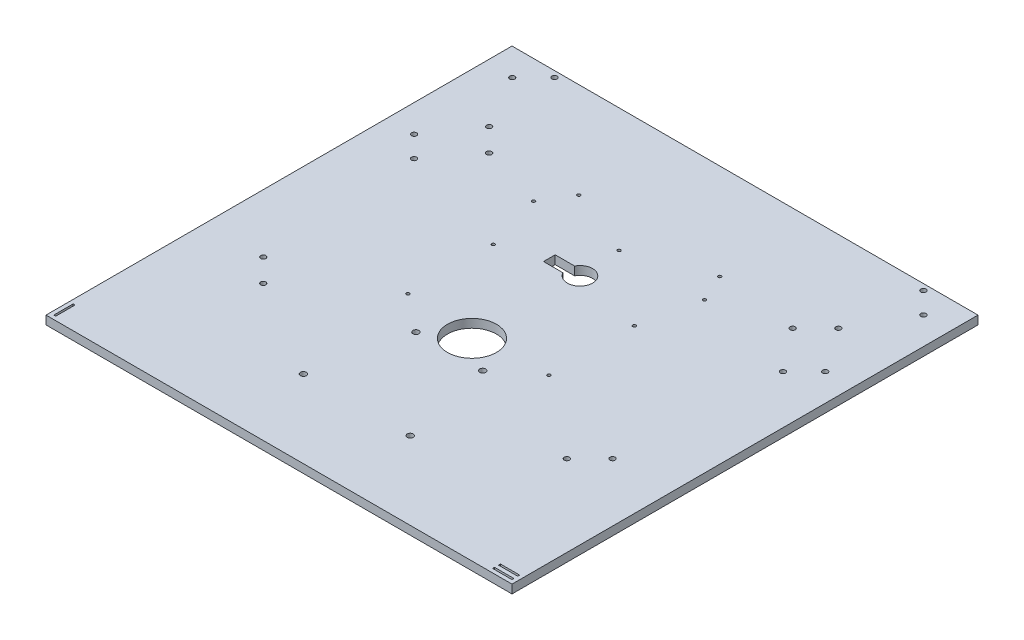
SolidWorks part; units mm, degrees
material "Acrylic (Medium-high impact)"
ref_plane "Front Plane" through (0, 0, 0) normal (0, 0, 1) x (1, 0, 0)
ref_plane "Top Plane" through (0, 0, 0) normal (0, 1, 0) x (1, 0, 0)
ref_plane "Right Plane" through (0, 0, 0) normal (1, 0, 0) x (0, 0, -1)
sketch "Sketch2" plane through (0, 0, 0) normal (0, 1, 0) x (1, 0, 0)
  line L1 (0, 0) -> (304.8, 0)
  line L2 (0, 0) -> (0, 304.8)
  line L3 (0, 304.8) -> (304.8, 304.8)
  line L4 (304.8, 0) -> (304.8, 304.8)
  dimension "D1" = 304.8
  dimension "D2" = 304.8
extrude "Boss-Extrude1" add sketch "Sketch2" along normal blind 5.588
sketch "Sketch4" plane through (0, 5.588, 0) normal (0, 1, 0) x (1, 0, 0)
  line L0 (0, 304.8) -> (0, 0) construction
  line L1 (2.54, 2.54) -> (3.81, 2.54)
  line L2 (2.54, 2.54) -> (2.54, 15.24)
  line L3 (2.54, 15.24) -> (3.81, 15.24)
  line L4 (3.81, 2.54) -> (3.81, 15.24)
  line L5 (2.54, 302.26) -> (3.81, 302.26) construction
  line L6 (2.54, 302.26) -> (2.54, 289.56) construction
  line L7 (2.54, 289.56) -> (3.81, 289.56) construction
  line L8 (3.81, 302.26) -> (3.81, 289.56) construction
  line L9 (6.35, 302.26) -> (7.62, 302.26) construction
  line L10 (6.35, 302.26) -> (6.35, 289.56) construction
  line L11 (6.35, 289.56) -> (7.62, 289.56) construction
  line L12 (7.62, 302.26) -> (7.62, 289.56) construction
  line L13 (304.8, 304.8) -> (0, 304.8) construction
  line L14 (0, 0) -> (304.8, 0) construction
  line L15 (304.8, 0) -> (304.8, 304.8) construction
  line L16 (302.26, 2.54) -> (289.56, 2.54)
  line L17 (302.26, 2.54) -> (302.26, 3.81)
  line L18 (302.26, 3.81) -> (289.56, 3.81)
  line L19 (289.56, 2.54) -> (289.56, 3.81)
  line L20 (302.26, 6.35) -> (289.56, 6.35)
  line L21 (302.26, 6.35) -> (302.26, 7.62)
  line L22 (302.26, 7.62) -> (289.56, 7.62)
  line L23 (289.56, 6.35) -> (289.56, 7.62)
  dimension "D1" = 12.7
  dimension "D2" = 1.27
  dimension "D3" = 2.54
  dimension "D4" = 2.54
  dimension "D5" = 2.54
  dimension "D6" = 2.54
  dimension "D7" = 2.54
  dimension "D8" = 2.54
  dimension "D9" = 2.54
  dimension "D10" = 2.54
extrude "Cut-Extrude1" cut sketch "Sketch4" against normal through all
sketch "Sketch5" plane through (0, 5.588, 0) normal (0, 1, 0) x (1, 0, 0)
  line L0 (0, 304.8) -> (0, 0) construction
  line L1 (34.5465, 268.1122) -> (263.4005, 268.1122)
  line L2 (34.5465, 268.1122) -> (34.5465, 281.0662)
  line L3 (34.5465, 281.0662) -> (263.4005, 281.0662)
  line L4 (263.4005, 268.1122) -> (263.4005, 281.0662)
  line L5 (304.8, 0) -> (304.8, 304.8) construction
  line L6 (304.8, 304.8) -> (0, 304.8) construction
  dimension "D1" = 34.5465
  dimension "D2" = 41.3995
  dimension "D3" = 23.7338
  dimension "D4" = 12.954
extrude "Cut-Extrude2" cut sketch "Sketch5" against normal blind 0.254
sketch "Sketch6" plane through (0, 5.588, 0) normal (0, 1, 0) x (1, 0, 0)
  circle A0 centre (152.48, 126.1263) radius 15.748 construction
  circle A1 centre (152.48, 126.1263) radius 15.748 construction
  circle A2 centre (152.48, 126.1263) radius 16.002
  circle A3 centre (31.75, 300.8321) radius 1.7 construction
  circle A4 centre (17.9387, 287.0209) radius 1.7 construction
  circle A5 centre (273.05, 300.8321) radius 1.7 construction
  circle A6 centre (286.8612, 287.0209) radius 1.7 construction
  circle A7 centre (286.8612, 222.7817) radius 1.7 construction
  circle A8 centre (273.05, 208.9705) radius 1.7 construction
  circle A9 centre (31.75, 208.9705) radius 1.7 construction
  circle A10 centre (17.9388, 222.7817) radius 1.7 construction
  circle A11 centre (31.75, 300.8321) radius 1.7
  circle A12 centre (17.9387, 287.0209) radius 1.7
  circle A13 centre (273.05, 300.8321) radius 1.7
  circle A14 centre (286.8612, 287.0209) radius 1.7
  circle A15 centre (286.8612, 222.7817) radius 1.7
  circle A16 centre (273.05, 208.9705) radius 1.7
  circle A17 centre (31.75, 208.9705) radius 1.7
  circle A18 centre (17.9388, 222.7817) radius 1.7
  circle A19 centre (38.1788, 103.933) radius 1.7 construction
  circle A20 centre (53.133, 88.9788) radius 1.7 construction
  circle A21 centre (251.667, 88.9788) radius 1.7 construction
  circle A22 centre (266.6212, 103.933) radius 1.7 construction
  circle A23 centre (266.6212, 251.667) radius 1.7 construction
  circle A24 centre (251.667, 236.7127) radius 1.7 construction
  circle A25 centre (53.133, 236.7127) radius 1.7 construction
  circle A26 centre (38.1788, 251.667) radius 1.7 construction
  circle A27 centre (38.1788, 103.933) radius 1.7
  circle A28 centre (53.133, 88.9788) radius 1.7
  circle A29 centre (251.667, 88.9788) radius 1.7
  circle A30 centre (266.6212, 103.933) radius 1.7
  circle A31 centre (266.6212, 251.667) radius 1.7
  circle A32 centre (251.667, 236.7127) radius 1.7
  circle A33 centre (53.133, 236.7127) radius 1.7
  circle A34 centre (38.1788, 251.667) radius 1.7
  circle A35 centre (117.555, 50.8216) radius 4.5 construction
  circle A36 centre (187.405, 50.8216) radius 4.5 construction
  circle A37 centre (174.3081, 111.328) radius 4.5 construction
  circle A38 centre (130.6519, 111.328) radius 4.5 construction
  circle A39 centre (117.555, 50.8216) radius 4.5 construction
  circle A40 centre (187.405, 50.8216) radius 4.5 construction
  circle A41 centre (174.3081, 111.328) radius 4.5 construction
  circle A42 centre (130.6519, 111.328) radius 4.5 construction
  circle A43 centre (130.6519, 111.328) radius 1.96
  circle A44 centre (174.3081, 111.328) radius 1.96
  circle A45 centre (187.405, 50.8216) radius 1.96
  circle A46 centre (117.555, 50.8216) radius 1.96
  dimension "D1" = 0.254
  dimension "D2" = 2.54
extrude "Cut-Extrude3" cut sketch "Sketch6" against normal through all
sketch "Sketch7" plane through (0, 5.588, 0) normal (0, 1, 0) x (1, 0, 0)
  line L0 (152.4, 304.8) -> (152.4, 0) construction
  line L1 (304.8, 304.8) -> (0, 304.8) construction
  line L2 (0, 0) -> (304.8, 0) construction
  line L4 (145.0768, 200.66) -> (132.3768, 200.66)
  line L5 (145.0768, 200.66) -> (145.0768, 193.04) construction
  line L6 (145.0768, 193.04) -> (132.3768, 193.04)
  line L7 (132.3768, 200.66) -> (132.3768, 193.04)
  circle A0 centre (152.4, 196.85) radius 8.255 construction
  arc A1 (145.0768, 200.66) -> (145.0768, 193.04) centre (152.4, 196.85) cw
  dimension "D2" = 16.51
  dimension "D1" = 107.95
  dimension "D3" = 7.62
  dimension "D4" = 12.7
extrude "Cut-Extrude4" cut sketch "Sketch7" against normal through all
sketch "Sketch8" plane through (0, 5.588, 0) normal (0, 1, 0) x (1, 0, 0)
  circle A0 centre (94.94, 223.995) radius 0.762 construction
  circle A1 centre (150.82, 223.995) radius 0.762 construction
  circle A2 centre (206.7, 223.995) radius 0.762 construction
  circle A3 centre (94.94, 223.995) radius 0.762 construction
  circle A4 centre (150.82, 223.995) radius 0.762 construction
  circle A5 centre (206.7, 223.995) radius 0.762 construction
  circle A6 centre (206.7, 223.995) radius 1.016
  circle A7 centre (150.82, 223.995) radius 1.016
  circle A8 centre (94.94, 223.995) radius 1.016
  dimension "D1" = 0.254
extrude "Cut-Extrude5" cut sketch "Sketch8" against normal through all
sketch "Sketch9" plane through (0, 5.588, 0) normal (0, 1, 0) x (1, 0, 0)
  circle A0 centre (106.3, 242.18) radius 0.762 construction
  circle A1 centre (106.3, 186.3) radius 0.762 construction
  circle A2 centre (106.3, 130.42) radius 0.762 construction
  circle A3 centre (198.5, 130.42) radius 0.762 construction
  circle A4 centre (198.5, 186.3) radius 0.762 construction
  circle A5 centre (198.5, 242.18) radius 0.762 construction
  circle A6 centre (106.3, 242.18) radius 0.762 construction
  circle A7 centre (106.3, 186.3) radius 0.762 construction
  circle A8 centre (106.3, 130.42) radius 0.762 construction
  circle A9 centre (198.5, 130.42) radius 0.762 construction
  circle A10 centre (198.5, 186.3) radius 0.762 construction
  circle A11 centre (198.5, 242.18) radius 0.762 construction
  circle A12 centre (106.3, 242.18) radius 1.016
  circle A13 centre (106.3, 186.3) radius 1.016
  circle A14 centre (106.3, 130.42) radius 1.016
  circle A15 centre (198.5, 130.42) radius 1.016
  circle A16 centre (198.5, 186.3) radius 1.016
  circle A17 centre (198.5, 242.18) radius 1.016
  dimension "D1" = 0.254
extrude "Cut-Extrude6" cut sketch "Sketch9" against normal through all
sketch "Sketch14" plane through (0, 5.588, 0) normal (0, 1, 0) x (1, 0, 0)
  line L0 (34.5465, 274.5892) -> (34.2925, 274.5892) construction
  line L1 (34.2925, 281.3386) -> (263.6545, 281.3386)
  line L2 (34.2925, 281.3386) -> (34.2925, 267.8399)
  line L3 (34.2925, 267.8399) -> (263.6545, 267.8399)
  line L4 (263.6545, 281.3386) -> (263.6545, 267.8399)
  line L5 (34.5465, 281.0662) -> (34.5465, 268.1122) construction
  line L6 (263.6545, 274.5892) -> (263.4005, 274.5892) construction
  line L7 (263.4005, 268.1122) -> (263.4005, 281.0662) construction
  dimension "D1" = 0.254
  dimension "D2" = 0.254
extrude "Boss-Extrude10" add sketch "Sketch14" against normal through all
equation "\"D8@Sketch4\"=\"D6@Sketch4\""
